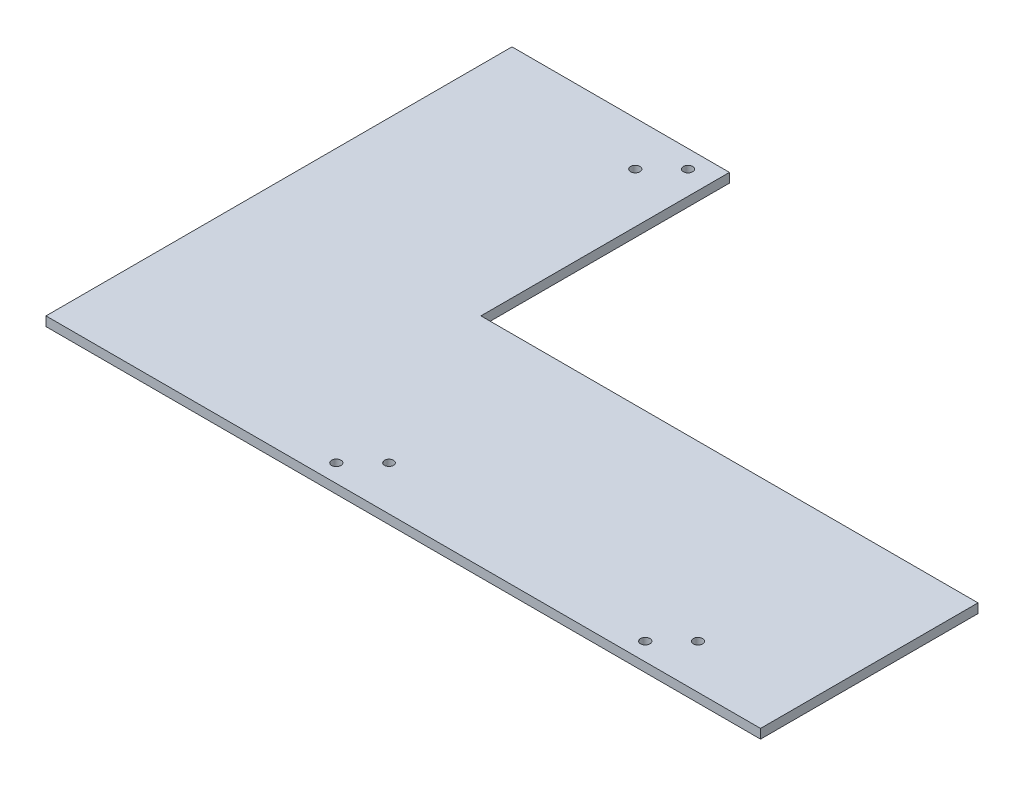
SolidWorks part; units mm, degrees
ref_plane "Front Plane" through (0, 0, 0) normal (0, 0, 1) x (1, 0, 0)
ref_plane "Top Plane" through (0, 0, 0) normal (0, 1, 0) x (1, 0, 0)
ref_plane "Right Plane" through (0, 0, 0) normal (1, 0, 0) x (0, 0, -1)
sketch "Sketch1" plane through (0, 0, 0) normal (0, 1, 0) x (1, 0, 0)
  line L0 (-115, -35) -> (115, -35)
  line L2 (-115, -35) -> (-115, 35)
  line L4 (115, -35) -> (115, 35)
  line L5 (-115, -35) -> (115, 35) construction
  line L6 (-115, 35) -> (115, -35) construction
  line L15 (-45, 35) -> (115, 35)
  line L17 (-115, 35) -> (-115, 115)
  line L18 (-115, 115) -> (-45, 115)
  line L19 (-45, 35) -> (-45, 115)
  circle A0 centre (-27.3165, -29.2426) radius 1.5
  circle A1 centre (-18.8312, -20.7574) radius 1.4446
  circle A2 centre (72.1317, -29.2426) radius 1.5
  circle A3 centre (80.617, -20.7574) radius 1.5
  circle A4 centre (-61.0737, 100.7574) radius 1.5
  circle A5 centre (-52.5884, 109.2426) radius 1.5
  point P0 (0, 0)
  dimension "D1" = 230
  dimension "D2" = 70
  dimension "D3" = 70
  dimension "D4" = 150
extrude "Boss-Extrude1" add sketch "Sketch1" along normal blind 3
